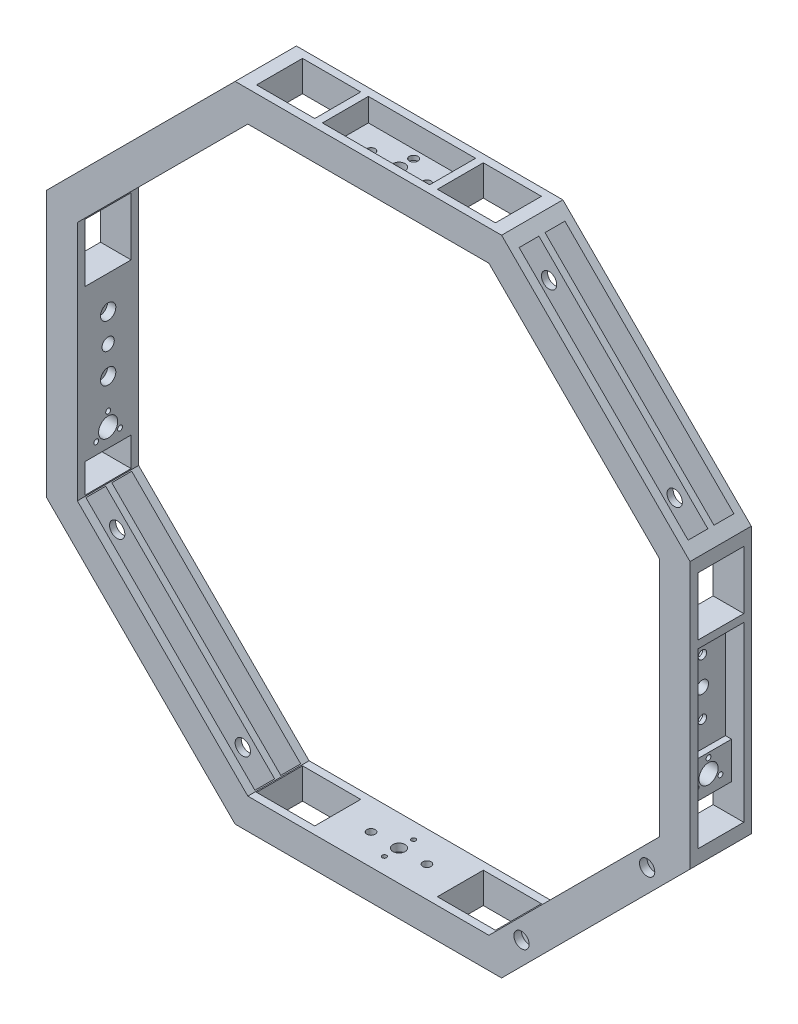
SolidWorks part; units mm, degrees
ref_plane "Plano frontal" through (0, 0, 0) normal (0, 0, 1) x (1, 0, 0)
ref_plane "Plano superior" through (0, 0, 0) normal (0, 1, 0) x (1, 0, 0)
ref_plane "Plano direito" through (0, 0, 0) normal (1, 0, 0) x (0, 0, -1)
sketch "Esboço1" plane through (0, 0, 0) normal (0, 0, 1) x (1, 0, 0)
  line L9 (210, 86.9848) -> (86.9848, 210)
  line L10 (86.9848, 210) -> (-86.9848, 210)
  line L11 (-86.9848, 210) -> (-210, 86.9848)
  line L12 (-210, 86.9848) -> (-210, -86.9848)
  line L13 (-210, -86.9848) -> (-86.9848, -210)
  line L14 (-86.9848, -210) -> (86.9848, -210)
  line L15 (86.9848, -210) -> (210, -86.9848)
  line L16 (210, -86.9848) -> (210, 86.9848)
  line L17 (190, 78.7006) -> (78.7006, 190)
  line L18 (78.7006, 190) -> (-78.7006, 190)
  line L19 (-78.7006, 190) -> (-190, 78.7006)
  line L20 (-190, 78.7006) -> (-190, -78.7006)
  line L21 (-190, -78.7006) -> (-78.7006, -190)
  line L22 (-78.7006, -190) -> (78.7006, -190)
  line L23 (78.7006, -190) -> (190, -78.7006)
  line L24 (190, -78.7006) -> (190, 78.7006)
  circle A0 centre (0, 0) radius 210 construction
  circle A1 centre (0, 0) radius 190 construction
extrude "Ressalto-extrusão1" add sketch "Esboço1" along normal blind 40
sketch "Esboço2" plane through (210, 0, 0) normal (1, 0, 0) x (0, 0, -1)
  line L1 (-4.9012, 78) -> (-4.9012, -78)
  line L23 (-4.9012, 78) -> (-34.9012, 78)
  line L24 (-34.9012, 78) -> (-34.9012, -78)
  line L25 (-4.9012, -78) -> (-34.9012, -78)
  line L26 (-4.9012, 78) -> (-4.9012, -78)
  line L27 (-4.9012, 78) -> (-34.9012, 78)
  line L28 (-34.9012, 78) -> (-34.9012, -78)
  line L29 (-4.9012, -78) -> (-34.9012, -78)
  line L30 (-4.9012, 0) -> (-4.9012, -59)
  line L31 (-34.9012, 0) -> (-34.9012, -59)
  line L32 (-4.9012, -59) -> (-34.9012, -59)
  line L33 (-4.9012, 0) -> (-4.9012, 40)
  line L34 (-34.9012, 0) -> (-34.9012, 40)
  line L35 (-4.9012, 40) -> (-34.9012, 40)
  line L36 (-4.9012, 35) -> (-4.9012, -35)
  line L37 (-4.9012, 35) -> (-34.9012, 35)
  line L38 (-34.9012, 35) -> (-34.9012, -35)
  line L39 (-4.9012, -35) -> (-34.9012, -35)
  circle A0 centre (-19.9012, 0) radius 4
  circle A1 centre (-19.9012, -18.25) radius 2.7
  circle A2 centre (-19.9012, 18.25) radius 2.7
  circle A8 centre (-19.9012, -38) radius 1.6
  circle A9 centre (-19.9012, -47) radius 6.25
  circle A10 centre (-12.107, -51.5) radius 1.6
  circle A11 centre (-27.6954, -51.5) radius 1.6
  point P30 (-19.9012, -47)
  dimension "D1" = 3
extrude "Corte-extrusão2" cut sketch "Esboço2" against normal up to next and the other way through all contours L1 L32 L24 L25 | A0 | A2 | A1 | L35 L1 L23 L24 region at (210, 59, 19.9012) region at (210, -68.5, 19.9012) region at (210, 0, 19.9012) region at (210, -18.25, 19.9012) region at (210, 18.25, 19.9012)
sketch "Esboço32" plane through (190, 0, 0) normal (-1, 0, 0) x (0, 0, 1)
  circle A0 centre (19.9012, 18.25) radius 2.7
  circle A1 centre (19.9012, -18.25) radius 2.7
hole_wizard "Rebaixo para parafuso Allen sextavado de M52" positions "Esboço33" profile "Esboço34" counterbore size "M5" standard "ISO" end condition up to next
sketch "Esboço33" plane through (190, 0, 0) normal (-1, 0, 0) x (0, 0, 1)
  point P0 (19.9012, 18.25)
  point P3 (19.9012, -18.25)
sketch "Esboço34" plane through (190, 18.25, 19.9012) normal (0, 1, 0) x (0, 0, 1)
  line L0 (0, 0) -> (0, 20)
  line L1 (0, 20) -> (2.75, 20)
  line L3 (2.75, 20) -> (2.75, 5.4)
  line L4 (2.75, 5.4) -> (5, 5.4)
  line L5 (5, 5.4) -> (5, 0)
  line L7 (5, 0) -> (0, 0)
  line L11 (0, -6.35) -> (0, 107.95) construction
  dimension "Thru Hole Dia." = 5.5
  dimension "Thru Hole Depth" = 20
  dimension "C'Bore Dia." = 10
  dimension "C'Bore Depth" = 5.4
extrude "Corte-extrusão15" cut sketch "Esboço2<6>" against normal up to next contours A8 | A9 | A10 | A11 region at (210, -38, 19.9012) region at (210, -47, 19.9012) region at (210, -51.5, 12.107) region at (210, -51.5, 27.6954)
sketch "Esboço2<6>" plane through (210, 0, 0) normal (1, 0, 0) x (0, 0, -1) same geometry as "Esboço2"
extrude "Corte-extrusão16" cut sketch "Esboço2<7>" against normal blind 8 contours L30 L39 L31 L32 A11 A10 A9 A8 region at (210, -47, 5.2854)
sketch "Esboço2<7>" plane through (210, 0, 0) normal (1, 0, 0) x (0, 0, -1) same geometry as "Esboço2"
sketch "Esboço15" plane through (-148.4924, 148.4924, 0) normal (-0.7071, 0.7071, 0) x (0, 0, 1)
  line L0 (40, 86.9848) -> (0, 86.9848) construction
  line L1 (5, 86.9848) -> (35, 86.9848)
  line L2 (5, 86.9848) -> (5, -86.9848)
  line L3 (5, -86.9848) -> (35, -86.9848)
  line L4 (35, 86.9848) -> (35, -86.9848)
  line L5 (40, -86.9848) -> (0, -86.9848) construction
  line L9 (20, 86.9848) -> (22, 86.9848)
  line L11 (20, -86.9848) -> (22, -86.9848)
  line L12 (22, 78) -> (22, -78)
  line L14 (20, 86.9848) -> (18, 86.9848)
  line L16 (20, -86.9848) -> (18, -86.9848)
  line L17 (18, 78) -> (18, -78)
  line L19 (5, 86.9848) -> (35, 86.9848)
  line L20 (5, 86.9848) -> (5, 78)
  line L21 (5, 78) -> (35, 78)
  line L22 (35, 86.9848) -> (35, 78)
  line L24 (5, -86.9848) -> (35, -86.9848)
  line L25 (5, -86.9848) -> (5, -78)
  line L26 (5, -78) -> (35, -78)
  line L27 (35, -86.9848) -> (35, -78)
extrude "Corte-extrusão5" cut sketch "Esboço15" against normal up to next contours L12 L26 L4 L21 | L2 L26 L17 L21 region at (-148.4924, 148.4924, 11.5) region at (-148.4924, 148.4924, 28.5)
sketch "Esboço16" plane through (148.4924, 148.4924, 0) normal (0.7071, 0.7071, 0) x (0, 0, -1)
  line L0 (-40, 86.9848) -> (0, 86.9848) construction
  line L2 (-34.9012, -78) -> (-34.9012, 86.9848)
  line L3 (-34.9012, 86.9848) -> (-5, 86.9848)
  line L4 (-5, -86.8738) -> (-5, 86.9848)
  line L8 (-34.9012, -78) -> (-5, -78)
  line L9 (-5, -86.8738) -> (-5, -78)
  line L10 (-5, 86.9848) -> (-34.9012, 86.9848)
  line L11 (-5, 86.9848) -> (-5, 78)
  line L12 (-5, 78) -> (-34.9012, 78)
  line L13 (-34.9012, 86.9848) -> (-34.9012, 78)
  line L14 (-19.9506, 78) -> (-18, 78)
  line L16 (-20, -78) -> (-18, -78)
  line L17 (-18, 78) -> (-18, -78)
  line L18 (-20, -78) -> (-22, -78)
  line L20 (-19.9506, 78) -> (-22, 78)
  line L21 (-22, -78) -> (-22, 78)
  line L22 (-34.9012, -78) -> (-5, -78)
  line L23 (-34.9012, -78) -> (-34.9012, -86.8738)
  line L24 (-34.9012, -86.8738) -> (-5, -86.8738)
  line L25 (-5, -78) -> (-5, -86.8738)
extrude "Corte-extrusão6" cut sketch "Esboço16" against normal through all both and the other way through all contours L8 L21 L12 L2 | L12 L17 L8 L4 region at (148.4924, 148.4924, 28.4506) region at (148.4924, 148.4924, 11.5)
sketch "Esboço18" plane through (0, -210, 0) normal (0, -1, 0) x (1, 0, 0)
  line L1 (-78, 35) -> (78, 35)
  line L2 (-78, 35) -> (-78, 5)
  line L3 (-78, 5) -> (78, 5)
  line L4 (78, 35) -> (78, 5)
  line L5 (-78, 35) -> (78, 35)
  line L6 (-78, 35) -> (-78, 5)
  line L7 (-78, 5) -> (78, 5)
  line L8 (78, 35) -> (78, 5)
  line L9 (0, 35) -> (40.0505, 35)
  line L11 (0, 5) -> (40.0505, 5)
  line L12 (40.0505, 35) -> (40.0505, 5)
  line L13 (0, 35) -> (-40, 35)
  line L15 (0, 5) -> (-40, 5)
  line L16 (-40, 35) -> (-40, 5)
  line L17 (-35, 35) -> (35, 35)
  line L18 (-35, 35) -> (-35, 5)
  line L19 (-35, 5) -> (35, 5)
  line L20 (35, 35) -> (35, 5)
  circle A0 centre (0, 20) radius 4
  circle A1 centre (18.25, 20) radius 2.7
  circle A2 centre (-18.25, 20) radius 2.7
  circle A3 centre (0, 29.53) radius 1.25
  circle A4 centre (0, 10.47) radius 1.25
  line M8 (86.9848, 0) -> (86.9848, 40)
  line M12 (-86.9848, 40) -> (-86.9848, 0)
sketch "Esboço26" plane through (0, 0, 0) normal (0, 0, -1) x (-1, 0, 0)
  circle A0 centre (100, 182) radius 5
  circle A1 centre (182, 100) radius 5
  circle A2 centre (-182, -100) radius 5
  circle A3 centre (-100, -182) radius 5
  circle A4 centre (100, -182) radius 5
  circle A5 centre (182, -100) radius 5
  circle A6 centre (-182, 100) radius 5
  circle A7 centre (-100, 182) radius 5
extrude "Corte-extrusão10" cut sketch "Esboço26" against normal up to next from surface starting at face at (141.4214, 141.4214, 18)
extrude "Corte-extrusão12" cut sketch "Esboço18" against normal through all contours L16 L1 L3 M12 | L1 L12 L3 M8 | A2 | A0 | A1 | A3 | A4 region at (-59, -210, 20) region at (59.0253, -210, 20) region at (0, -210, 20) region at (18.25, -210, 20) region at (-18.25, -210, 20) region at (0, -210, 29.53) region at (0, -210, 10.47)
extrude "Corte-extrusão13" cut sketch "Esboço18<4>" against normal blind 15 contours L20 L5 L13 L18 L15 L7 A2 A1 A0 region at (-17.5, -210, 34.2384)
sketch "Esboço18<4>" plane through (0, -210, 0) normal (0, -1, 0) x (1, 0, 0) same geometry as "Esboço18"
extrude "Corte-extrusão14" cut sketch "Esboço2<5>" against normal blind 12 contours L39 L26 L33 L37 L34 L28 A2 A1 A0 region at (210, 17.5, 5.6628)
sketch "Esboço2<5>" plane through (210, 0, 0) normal (1, 0, 0) x (0, 0, -1) same geometry as "Esboço2"
mirror "Espelhar6" about plane through (0, 0, 0) normal (1, 0, 0) of "Rebaixo para parafuso Allen sextavado de M52", "Corte-extrusão2", "Corte-extrusão14", "Corte-extrusão15", "Corte-extrusão16"
hole_wizard "Rebaixo para parafuso Allen sextavado de M2.51" positions "Esboço35" profile "Esboço36" counterbore size "M2.5" standard "ISO" end condition up to next
sketch "Esboço35" plane through (0, -195, 0) normal (0, -1, 0) x (-1, 0, 0)
  point P0 (0, -10.47)
  point P3 (0, -29.53)
sketch "Esboço36" plane through (0, -195, 10.47) normal (1, 0, 0) x (0, 0, -1)
  line L0 (0, 0) -> (0, 405)
  line L1 (0, 405) -> (1.45, 405)
  line L3 (1.45, 405) -> (1.45, 2.9)
  line L4 (1.45, 2.9) -> (2.75, 2.9)
  line L5 (2.75, 2.9) -> (2.75, 0)
  line L7 (2.75, 0) -> (0, 0)
  line L11 (0, -6.35) -> (0, 107.95) construction
  dimension "Thru Hole Dia." = 2.9
  dimension "Thru Hole Depth" = 405
  dimension "C'Bore Dia." = 5.5
  dimension "C'Bore Depth" = 2.9
ref_plane "Plano1" through (0, 0, 0) normal (-0.7071, 0.7071, 0) x (0.7071, 0.7071, 0)
mirror "Espelhar8" about plane through (0, 0, 0) normal (-0.7071, 0.7071, 0) of "Corte-extrusão5"
mirror "Espelhar9" about plane through (0, 0, 0) normal (0, 1, 0) of "Rebaixo para parafuso Allen sextavado de M2.51", "Corte-extrusão12", "Corte-extrusão13"
